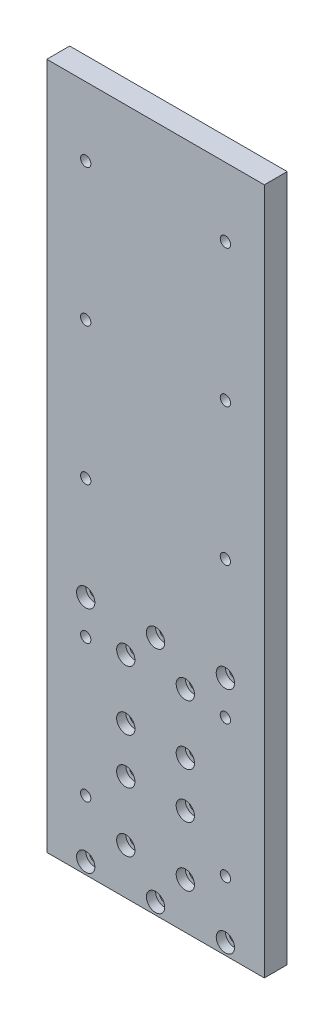
SolidWorks part; units mm, degrees
ref_plane "Piano frontale" through (0, 0, 0) normal (0, 0, 1) x (1, 0, 0)
ref_plane "Piano superiore" through (0, 0, 0) normal (0, 1, 0) x (1, 0, 0)
ref_plane "Piano destro" through (0, 0, 0) normal (1, 0, 0) x (0, 0, -1)
sketch "Schizzo1" plane through (0, 0, 0) normal (0, 0, 1) x (1, 0, 0)
  line L1 (0, 0) -> (95, 0)
  line L2 (0, 0) -> (0, 300)
  line L3 (0, 300) -> (95, 300)
  line L4 (95, 0) -> (95, 300)
  dimension "D1" = 95
  dimension "D2" = 300
extrude "Estrusione-Estrusione1" add sketch "Schizzo1" against normal blind 10
sketch "Schizzo2" plane through (0, 0, 0) normal (0, 0, 1) x (1, 0, 0)
  line L0 (0, 0) -> (104.4353, 0) construction
  line L1 (0, 5) -> (104.4353, 5) construction
  line L2 (23.1648, 20) -> (74.0129, 20) construction
  line L3 (23.1648, 46) -> (74.0129, 46) construction
  line L4 (23.1648, 66) -> (74.0129, 66) construction
  line L5 (23.1648, 92) -> (74.0129, 92) construction
  line L6 (6.7858, 105) -> (86.7249, 105) construction
  line L11 (0, 92) -> (144.5719, 92) construction
  line L12 (0, 66) -> (144.5719, 66) construction
  line L14 (47.5, 0) -> (47.5, 300) construction
  line L15 (0, 46) -> (144.5719, 46) construction
  line L16 (34.5, 0.6985) -> (34.5, 300) construction
  line L17 (60.5, 0) -> (60.5, 250) construction
  line L19 (0, 20) -> (144.5719, 20) construction
  line L20 (0, 5) -> (144.5719, 5) construction
  line L21 (0, 0) -> (144.5719, 0) construction
  line L22 (0, 105) -> (144.5719, 105) construction
  line L23 (95, 300) -> (0, 300) construction
  circle A0 centre (17, 105) radius 2.25
  circle A1 centre (17, 5) radius 2.25
  circle A2 centre (34.5, 20) radius 2.25
  circle A3 centre (34.5, 46) radius 2.25
  circle A4 centre (34.5, 66) radius 2.25
  circle A5 centre (34.5, 92) radius 2.25
  circle A6 centre (47.5, 105) radius 2.25
  circle A7 centre (47.5, 5) radius 2.25
  circle A8 centre (60.5, 92) radius 2.25
  circle A9 centre (60.5, 66) radius 2.25
  circle A10 centre (60.5, 46) radius 2.25
  circle A11 centre (60.5, 20) radius 2.25
  circle A12 centre (78, 5) radius 2.25
  circle A13 centre (78, 105) radius 2.25
  dimension "D7" = 4.5
  dimension "D8" = 13
  dimension "D2" = 26
  dimension "D3" = 26
  dimension "D4" = 20
  dimension "D5" = 20
  dimension "D9" = 30.5
  dimension "D10" = 30.5
  dimension "D1" = 5
  dimension "D6" = 105
extrude "Taglio-Estrusione1" cut sketch "Schizzo2" against normal through all
sketch "Schizzo4" plane through (0, 0, 0) normal (0, 0, 1) x (1, 0, 0)
  circle A0 centre (17, 105) radius 4
  circle A1 centre (47.5, 105) radius 4
  circle A2 centre (78, 105) radius 4
  circle A3 centre (34.5, 92) radius 4
  circle A4 centre (60.5, 92) radius 4
  circle A5 centre (34.5, 66) radius 4
  circle A6 centre (60.5, 66) radius 4
  circle A7 centre (34.5, 46) radius 4
  circle A8 centre (60.5, 46) radius 4
  circle A9 centre (17, 5) radius 4
  circle A10 centre (34.5, 20) radius 4
  circle A11 centre (60.5, 20) radius 4
  circle A12 centre (47.5, 5) radius 4
  circle A13 centre (78, 5) radius 4
  dimension "D1" = 8
extrude "Taglio-Estrusione2" cut sketch "Schizzo4" against normal blind 4
sketch "Schizzo5" plane through (0, 0, 0) normal (0, 0, 1) x (1, 0, 0)
  line L0 (0, 150) -> (95, 150) construction
  line L1 (0, 300) -> (0, 0) construction
  line L2 (95, 0) -> (95, 300) construction
  line L3 (78, 300) -> (78, 0) construction
  line L4 (95, 300) -> (0, 300) construction
  line L5 (0, 0) -> (104.4353, 0) construction
  line L6 (47.5, 0) -> (47.5, 300) construction
  line L7 (47.5, 300) -> (47.5, 0) construction
  circle A0 centre (78, 150) radius 2
  circle A1 centre (78, 210) radius 2
  circle A2 centre (78, 270) radius 2
  circle A3 centre (78, 30) radius 2
  circle A4 centre (78, 90) radius 2
  circle A5 centre (17, 90) radius 2
  circle A6 centre (17, 30) radius 2
  circle A7 centre (17, 270) radius 2
  circle A8 centre (17, 210) radius 2
  circle A9 centre (17, 150) radius 2
  point P18 (78, 150)
  dimension "D1" = 4
  dimension "D2" = 30.5
  dimension "D3" = 3
extrude "Taglio-Estrusione3" cut sketch "Schizzo5" against normal through all
hole_wizard "Foro per Vite M4-1" positions "Schizzo3D1" profile "Schizzo6" hole size "M4" standard "Ansi Metric"
sketch3d "Schizzo3D1"
  line L0 (17, 270, -10) -> (17, 270, 0) construction
  line L1 (78, 270, -10) -> (78, 270, 0) construction
  line L2 (17, 210, -10) -> (17, 210, 0) construction
  line L3 (78, 210, -10) -> (78, 210, 0) construction
  line L4 (17, 150, -10) -> (17, 150, 0) construction
  line L5 (78, 150, -10) -> (78, 150, 0) construction
  line L6 (17, 90, -10) -> (17, 90, 0) construction
  line L7 (78, 90, -10) -> (78, 90, 0) construction
  line L8 (17, 30, -10) -> (17, 30, 0) construction
  line L9 (78, 30, -10) -> (78, 30, 0) construction
  point P0 (17, 270, 0)
  point P4 (78, 270, 0)
  point P8 (17, 210, 0)
  point P12 (78, 210, 0)
  point P16 (17, 150, 0)
  point P20 (78, 150, 0)
  point P24 (17, 90, 0)
  point P28 (78, 90, 0)
  point P33 (17, 30, 0)
  point P37 (78, 30, 0)
sketch "Schizzo6" plane through (17, 270, 0) normal (1, 0, 0) x (0, -1, 0)
  line L0 (0, 0) -> (0, 11.3519)
  line L1 (0, 11.3519) -> (2.25, 10)
  line L2 (2.25, 10) -> (2.25, 0)
  line L5 (2.25, 0) -> (0, 0)
  line L10 (0, 11.3519) -> (-2.25, 10) construction
  line L11 (0, -6.35) -> (0, 107.95) construction
  dimension "Hole Dia." = 4.5
  dimension "Hole Depth" = 10
  dimension "Drill Angle" = 118
